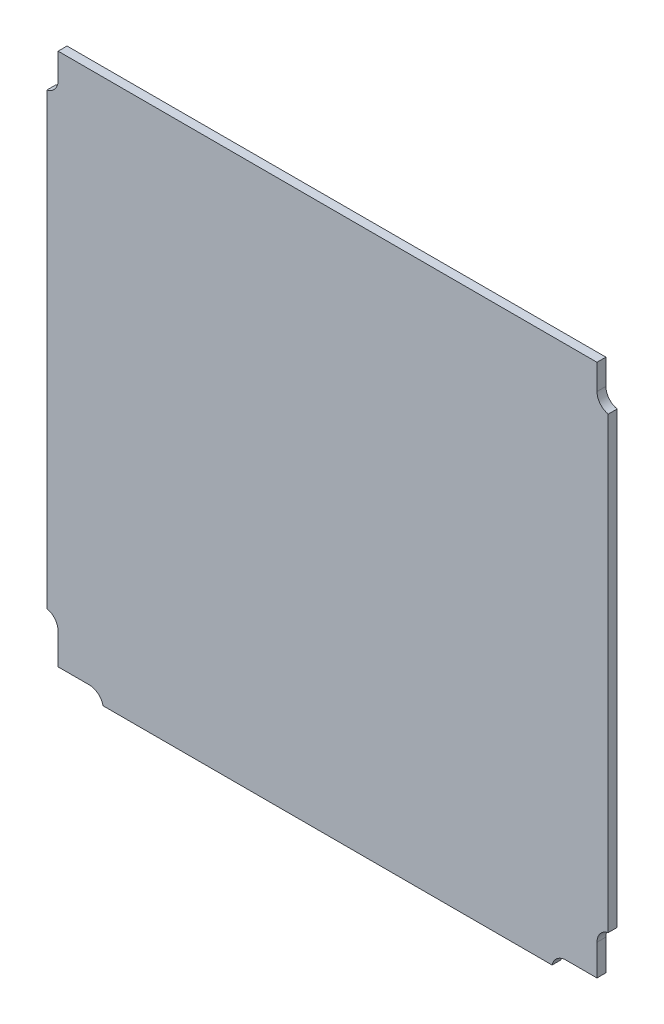
SolidWorks part; units mm, degrees
ref_plane "Front Plane" through (0, 0, 0) normal (0, 0, 1) x (1, 0, 0)
ref_plane "Top Plane" through (0, 0, 0) normal (0, 1, 0) x (1, 0, 0)
ref_plane "Right Plane" through (0, 0, 0) normal (1, 0, 0) x (0, 0, -1)
sketch "Sketch1" plane through (0, 0, 0) normal (0, 0, 1) x (1, 0, 0)
  line L1 (-50, -50) -> (50, -50)
  line L2 (-50, -50) -> (-50, 40)
  line L4 (50, -50) -> (50, 40)
  line L5 (-50, -50) -> (50, 50) construction
  line L6 (-50, 50) -> (50, -50) construction
  line L10 (-48, 47) -> (-48, 40)
  line L13 (-48, 40) -> (-50, 40)
  line L14 (50, 40) -> (48, 40)
  line L15 (-50, -50) -> (-37.8649, -50)
  line L16 (-50, -50) -> (-50, -37.8649)
  line L19 (50, -50) -> (41.5, -50)
  line L20 (50, -50) -> (50, -41.5)
  line L21 (48, 40) -> (48, 47)
  line L24 (40, -50) -> (40, -48)
  line L25 (50, -50) -> (40, -50)
  line L26 (50, -50) -> (50, -40)
  line L27 (40, -48) -> (48, -48)
  line L28 (48, -48) -> (48, -40)
  line L29 (48, -40) -> (50, -40)
  line L30 (-50, -40) -> (-48, -40)
  line L31 (-50, -50) -> (-50, -40)
  line L32 (-50, -50) -> (-40, -50)
  line L33 (-48, -40) -> (-48, -48)
  line L34 (-48, -48) -> (-40, -48)
  line L35 (-40, -48) -> (-40, -50)
  line L36 (48, 47) -> (-48, 47)
  line L38 (48, 48) -> (40, 48) [skipped]
  line L39 (40, 48) -> (40, 50) [skipped]
  point P0 (0, 0)
  point P38 (0, 0)
  dimension "D1" = 100
  dimension "D2" = 2
  dimension "D3" = 7
  dimension "D4" = 10
  dimension "D6" = 97
  dimension "D7" = 10
  dimension "D8" = 2
  dimension "D9" = 50
  dimension "D10" = 50
  dimension "D11" = 10
  dimension "D5" = 4
extrude "Boss-Extrude1" add sketch "Sketch1" along normal blind 1.5875 contours L1 L4 L2 region at (0, -1.2917, 0)
fillet "Fillet1" radius 2.54 6 edges at (-48, -40, 0.7937) (-40, -48, 0.7937) (40, -48, 0.7937) (48, -40, 0.7937) (48, 40, 0.7937) (-48, 40, 0.7937)
